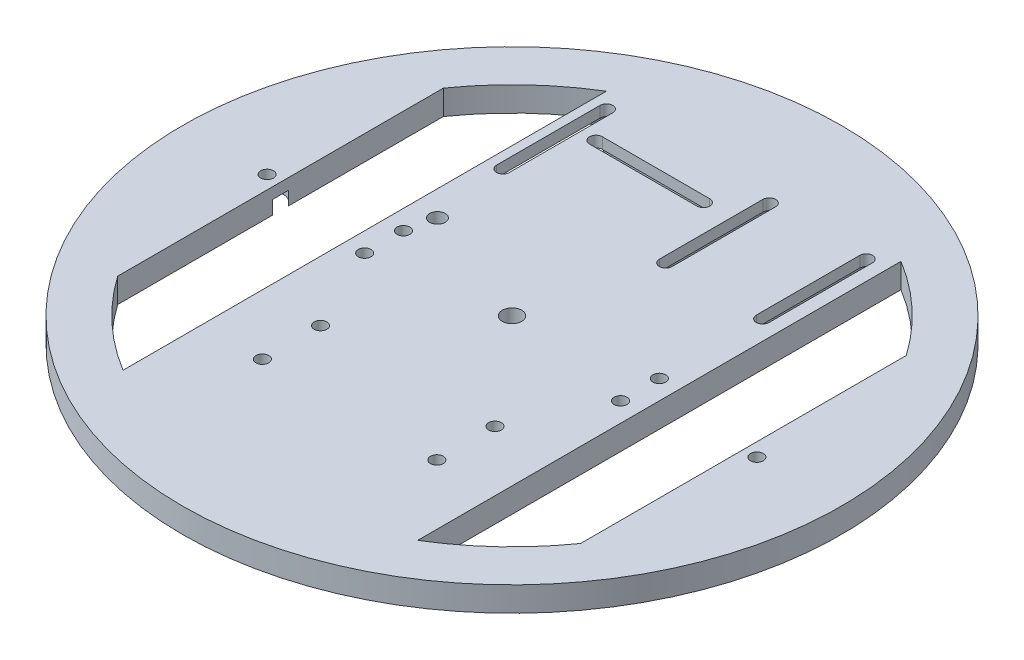
SolidWorks part; units mm, degrees
material "Delrin 2700 NC010, Low Viscosity Acetal Copolymer (SS)"
ref_plane "Front Plane" through (0, 0, 0) normal (0, 0, 1) x (1, 0, 0)
ref_plane "Top Plane" through (0, 0, 0) normal (0, 1, 0) x (1, 0, 0)
ref_plane "Right Plane" through (0, 0, 0) normal (1, 0, 0) x (0, 0, -1)
sketch "Sketch1" plane through (0, 0, 0) normal (0, 1, 0) x (1, 0, 0)
  line L0 (0, 85) -> (0, -85) construction
  line L1 (0, 0) -> (38, 0) construction
  line L2 (-38, 62.3298) -> (-38, -62.3298)
  line L3 (-59.7076, -42) -> (-59.7076, 42)
  line L4 (38, 62.3298) -> (38, -62.3298)
  line L5 (-38, 62.3298) -> (38, -62.3298) construction
  line L6 (-38, -62.3298) -> (38, 62.3298) construction
  line L7 (59.7076, -42) -> (59.7076, 42)
  circle A0 centre (0, 0) radius 85
  arc A1 (38, -62.3298) -> (59.7076, -42) centre (0, 0) ccw
  arc A2 (-38, 62.3298) -> (-59.7076, 42) centre (0, 0) ccw
  circle A3 centre (0, 0) radius 2.5
  circle A4 centre (-31.48, 12.25) radius 2
  arc A5 (-59.7076, -42) -> (-38, -62.3298) centre (0, 0) ccw
  arc A6 (59.7076, 42) -> (38, 62.3298) centre (0, 0) ccw
  dimension "D1" = 170
  dimension "D2" = 12
  dimension "D4" = 5
  dimension "D5" = 4
  dimension "D3" = 76
  dimension "D6" = 6.52
  dimension "D7" = 12.25
  dimension "D8" = 84
  dimension "D9" = 84
extrude "Boss-Extrude1" add sketch "Sketch1" along normal blind 6.35
hole_wizard "CBORE for M3 SHCS1" positions "Sketch2" profile "Sketch3" counterbore size "M3" standard "ANSI Metric" end condition through all
sketch "Sketch2" plane through (0, 0, 0) normal (0, -1, 0) x (-1, 0, 0)
  line L0 (0, 0) -> (-38, 0) construction
  line L1 (-38, 62.3298) -> (-38, -62.3298) construction
  line L3 (0, 0) -> (0, 85) construction
  line L4 (-59.7076, -42) -> (-59.7076, 42) construction
  line L5 (-38, 0) -> (-85, 0) construction
  circle A0 centre (0, 0) radius 85 construction
  point P0 (-33, 5)
  point P19 (-33, -5)
  point P21 (33, 5)
  point P22 (33, -5)
  point P23 (63.1576, 0)
  point P28 (-63.1576, 0)
  dimension "D1" = 10
  dimension "D2" = 5
  dimension "D4" = 3.45
sketch "Sketch3" plane through (33, 0, -5) normal (1, 0, 0) x (0, 0, -1)
  line L0 (0, 0) -> (0, 6.35)
  line L1 (0, 6.35) -> (1.65, 6.35)
  line L3 (1.65, 6.35) -> (1.65, 3.5)
  line L4 (1.65, 3.5) -> (4, 3.5)
  line L5 (4, 3.5) -> (4, 0)
  line L7 (4, 0) -> (0, 0)
  line L11 (0, -6.35) -> (0, 107.95) construction
  dimension "Thru Hole Dia." = 3.3
  dimension "Thru Hole Depth" = 6.35
  dimension "C'Bore Dia." = 8
  dimension "C'Bore Depth" = 3.5
hole_wizard "CBORE for M3 SHCS2" positions "Sketch5" profile "Sketch6" counterbore size "M3" standard "ANSI Metric" end condition through all
sketch "Sketch5" plane through (0, 0, 0) normal (0, -1, 0) x (-1, 0, 0)
  line L0 (0, 0) -> (0, -85) construction
  line L3 (0, -43.6871) -> (-33, -43.6871) construction
  circle A0 centre (0, 0) radius 85 construction
  point P0 (22.5, -26.8871)
  point P12 (-22.5, -26.8871)
  point P33 (22.5, -41.8871)
  point P34 (-22.5, -41.8871)
  dimension "D1" = 45
  dimension "D2" = 16.8
  dimension "D3" = 54.75
  dimension "D4" = 10.5
  dimension "D5" = 2
sketch "Sketch6" plane through (-22.5, 0, 26.8871) normal (1, 0, 0) x (0, 0, -1)
  line L0 (0, 0) -> (0, 6.35)
  line L1 (0, 6.35) -> (1.65, 6.35)
  line L3 (1.65, 6.35) -> (1.65, 3.5)
  line L4 (1.65, 3.5) -> (4, 3.5)
  line L5 (4, 3.5) -> (4, 0)
  line L7 (4, 0) -> (0, 0)
  line L11 (0, -6.35) -> (0, 107.95) construction
  dimension "Thru Hole Dia." = 3.3
  dimension "Thru Hole Depth" = 6.35
  dimension "C'Bore Dia." = 8
  dimension "C'Bore Depth" = 3.5
hole_wizard "CBORE SLOT for M3 SHCS1" positions "Sketch12" profile "Sketch13" size "M3" standard "ANSI Metric" slot yes end condition through all
sketch "Sketch12" plane through (0, 0, 0) normal (0, -1, 0) x (-1, 0, 0)
  line L0 (-33, 30) -> (-33, 60) construction
  line L2 (-38, 62.3298) -> (-38, -62.3298) construction
  line L3 (38, -62.3298) -> (38, 62.3298) construction
  point P0 (-33, 45)
  point P4 (-8, 45)
  point P23 (34, 45)
  dimension "D1" = 30
  dimension "D2" = 25
  dimension "D3" = 5
  dimension "D4" = 45
  dimension "D5" = 45
  dimension "D6" = 45
  dimension "D7" = 4
sketch "Sketch13" plane through (33, 0, -45) normal (1, 0, 0) x (0, 0, -1)
  line L0 (0, 0) -> (0, 6.35)
  line L1 (0, 6.35) -> (1.65, 6.35)
  line L3 (1.65, 6.35) -> (1.65, 3.5)
  line L4 (1.65, 3.5) -> (4, 3.5)
  line L5 (4, 3.5) -> (4, 0)
  line L7 (4, 0) -> (0, 0)
  line L11 (0, -6.35) -> (0, 107.95) construction
  dimension "Thru Hole Dia." = 3.3
  dimension "Thru Hole Depth" = 6.35
  dimension "C'Bore Dia." = 8
  dimension "C'Bore Depth" = 3.5
hole_wizard "CBORE SLOT for M3 SHCS2" positions "Sketch14" profile "Sketch15" size "M3" standard "ANSI Metric" slot yes end condition through all
sketch "Sketch14" plane through (0, 0, 0) normal (0, -1, 0) x (-1, 0, 0)
  line L0 (30, 50) -> (-1, 50) construction
  line L1 (38, 58.35) -> (38, 62.3298) construction
  line L2 (0, 0) -> (85, 0) construction
  circle A0 centre (0, 0) radius 85 construction
  point P0 (14.5, 50)
  dimension "D1" = 31
  dimension "D2" = 0
  dimension "D3" = 8
  dimension "D4" = 50
  dimension "D5" = 0
sketch "Sketch15" plane through (-14.5, 0, -50) normal (1, 0, 0) x (0, 0, -1)
  line L0 (0, 0) -> (0, 6.35)
  line L1 (0, 6.35) -> (1.65, 6.35)
  line L3 (1.65, 6.35) -> (1.65, 3.5)
  line L4 (1.65, 3.5) -> (4, 3.5)
  line L5 (4, 3.5) -> (4, 0)
  line L7 (4, 0) -> (0, 0)
  line L11 (0, -6.35) -> (0, 107.95) construction
  dimension "Thru Hole Dia." = 3.3
  dimension "Thru Hole Depth" = 6.35
  dimension "C'Bore Dia." = 8
  dimension "C'Bore Depth" = 3.5
sketch "Sketch16" plane through (0, 0, 0) normal (0, -1, 0) x (1, 0, 0)
  line L0 (0, 0) -> (38, 0) construction
  line L1 (38, -62.3298) -> (38, 62.3298) construction
  line L2 (0, -85) -> (0, 85) construction
  circle A0 centre (0, 0) radius 85 construction
  circle A1 centre (0, -70) radius 1.65
  circle A2 centre (0, 70) radius 1.65
  dimension "D1" = 3.3
  dimension "D2" = 70
extrude "Cut-Extrude1" cut sketch "Sketch16" against normal blind 1
